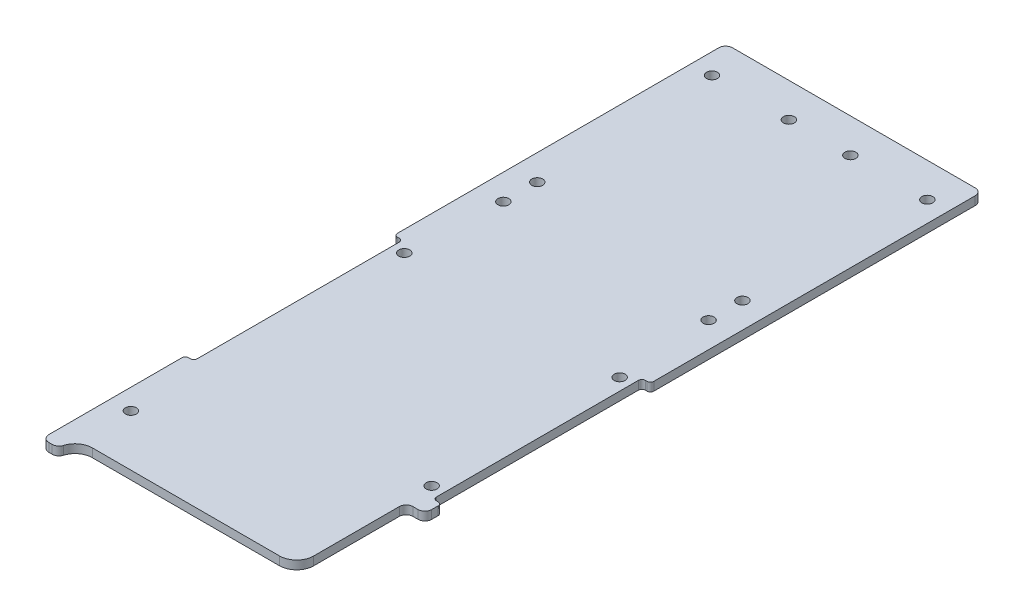
SolidWorks part; units mm, degrees
ref_plane "Front Plane" through (0, 0, 0) normal (0, 0, 1) x (1, 0, 0)
ref_plane "Top Plane" through (0, 0, 0) normal (0, 1, 0) x (1, 0, 0)
ref_plane "Right Plane" through (0, 0, 0) normal (1, 0, 0) x (0, 0, -1)
sketch "Sketch1" plane through (0, 0, 0) normal (0, 1, 0) x (1, 0, 0)
  line L0 (-39.9997, 0) -> (-39.9997, 114.3) construction
  line L1 (-47.625, 127) -> (47.625, 127)
  line L2 (-47.625, 127) -> (-47.625, -127)
  line L3 (-47.625, -127) -> (47.625, -127)
  line L4 (47.625, 127) -> (47.625, -127)
  line L5 (-47.625, 127) -> (47.625, -127) construction
  line L6 (-47.625, -127) -> (47.625, 127) construction
  line L7 (0, 0) -> (0, 127) construction
  line L8 (-39.9997, 0) -> (-39.9997, -101.6) construction
  line L9 (-39.9997, 0) -> (0, 0) construction
  line L10 (-41.275, -127) -> (-41.275, -120.65)
  line L11 (-41.275, -120.65) -> (41.275, -120.65)
  line L12 (41.275, -120.65) -> (41.275, -127)
  line L13 (-39.9997, 114.3) -> (-11.4247, 114.3) construction
  line L14 (39.9997, 114.3) -> (11.4247, 114.3) construction
  circle A0 centre (-39.9997, 114.3) radius 2.032
  circle A1 centre (-39.9997, 0) radius 2.032
  circle A2 centre (-39.9997, -101.6) radius 2.032
  circle A3 centre (39.9997, -101.6) radius 2.032
  circle A4 centre (39.9997, 0) radius 2.032
  circle A5 centre (39.9997, 114.3) radius 2.032
  circle A6 centre (-11.4247, 114.3) radius 2.032
  circle A7 centre (11.4247, 114.3) radius 2.032
  circle A8 centre (-39.9997, -69.85) radius 2.032
  circle A9 centre (39.9997, -69.85) radius 2.032
  point P0 (0, 0)
  dimension "D4" = 4.064
  dimension "D10" = 28.575
  dimension "D1" = 95.25
  dimension "D2" = 254
  dimension "D3" = 7.6253
  dimension "D5" = 12.7
  dimension "D6" = 25.4
  dimension "D7" = 6.35
  dimension "D8" = 6.35
  dimension "D9" = 6.35
  dimension "D11" = 69.85
extrude "Boss-Extrude1" add sketch "Sketch1" along normal blind 3.175 contours L4 L1 L2 L3 A4 A0 A1 A2 A3 A5 | A8 | A3 region at (0, 0, -2.6944) region at (39.9997, 0, 101.6) region at (-39.9997, 0, 69.85)
fillet "Fillet1" radius 2.54 4 edges at (-47.625, 1.5875, -127) (47.625, 1.5875, -127) (47.625, 1.5875, 127) (-47.625, 1.5875, 127)
fillet "Fillet2" radius 2.54 2 edges at (41.275, 1.5875, 127) (-41.275, 1.5875, 127)
fillet "Fillet3" radius 6.35 2 edges at (41.275, 1.5875, 120.65) (-41.275, 1.5875, 120.65)
sketch "Sketch2" plane through (0, 0, 0) normal (0, -1, 0) x (1, 0, 0)
  line L0 (41.9119, 131.8831) -> (41.9119, 109.8659) construction
  line L1 (41.9119, 109.8659) -> (41.9119, 106.3879) construction
  line L2 (41.9119, 83.271) -> (41.9119, 82.5325) construction
  line L3 (41.9119, 82.5325) -> (41.9119, 81.2514) construction
  line L4 (41.9119, 83.271) -> (41.9119, 106.3879) construction
  line L5 (41.9119, 131.8831) -> (41.9119, 109.8659)
  line L6 (41.9119, 109.8659) -> (41.9119, 106.3879)
  line L7 (41.9119, 83.271) -> (41.9119, 82.5325)
  line L8 (41.9119, 82.5325) -> (41.9119, 81.2514)
  line L9 (41.9119, 83.271) -> (41.9119, 106.3879)
  line L10 (41.9119, 81.2514) -> (47.625, 81.2514)
  line L11 (47.625, -124.46) -> (47.625, 124.46) construction
  line L12 (41.9119, 131.8831) -> (47.625, 131.8831)
  line L13 (47.625, 131.8831) -> (47.625, 81.2514)
  line L14 (40.6419, 79.9814) -> (48.895, 79.9814)
  line L15 (48.895, 133.1531) -> (48.895, 79.9814)
  line L16 (40.6419, 133.1531) -> (48.895, 133.1531)
  line L17 (40.6419, 133.1531) -> (40.6419, 109.8659)
  line L18 (40.6419, 109.8659) -> (40.6419, 106.3879)
  line L19 (40.6419, 83.271) -> (40.6419, 106.3879)
  line L20 (40.6419, 83.271) -> (40.6419, 82.5325)
  line L21 (40.6419, 82.5325) -> (40.6419, 79.9814)
  arc M7 (43.815, 127) -> (41.3809, 125.1857) centre (43.815, 124.46) ccw
  arc M8 (41.3809, 125.1857) -> (35.2956, 120.65) centre (35.2956, 127) cw
  line M18 (47.625, -124.46) -> (47.625, 124.46)
  dimension "D1" = 1.27
extrude "Cut-Extrude1" cut sketch "Sketch2" against normal through all contours L20 L21 L14 L10 L8 L7 L9 L19 M18 | L19 L9 L6 L5 L17 L18 M7 M8 | L13 L10 L8 L7 L9 L6 L5 L12 region at (41.6768, 0, 99.9813)
fillet "Fillet4" radius 6.35 1 edges at (40.6419, 1.5875, 123.5737)
fillet "Fillet5" radius 2.54 2 edges at (47.625, 1.5875, 79.9814) (40.6419, 1.5875, 79.9814)
sketch "Sketch3" plane through (0, 0, 0) normal (0, -1, 0) x (1, 0, 0)
  line L0 (-36.3087, -49.7791) -> (-39.9155, -49.7791) construction
  line L1 (-40.4235, -49.276) -> (-40.4235, -45.7043) construction
  line L2 (-35.8007, -45.7043) -> (-35.8007, -49.276) construction
  line L3 (-39.9155, -45.2013) -> (-36.3087, -45.2013) construction
  line L4 (-36.3087, -37.2027) -> (-39.9155, -37.2027) construction
  line L5 (-35.8007, -33.1279) -> (-35.8007, -36.6996) construction
  line L6 (-40.4235, -36.6996) -> (-40.4235, -33.1279) construction
  line L7 (-39.9155, -32.6249) -> (-36.3087, -32.6249) construction
  line L8 (36.2845, -32.6249) -> (39.8913, -32.6249) construction
  line L9 (40.3993, -33.1279) -> (40.3993, -36.6996) construction
  line L10 (39.8913, -37.2027) -> (36.2845, -37.2027) construction
  line L11 (35.7765, -36.6996) -> (35.7765, -33.1279) construction
  line L12 (36.2845, -45.2013) -> (39.8913, -45.2013) construction
  line L13 (35.7765, -49.276) -> (35.7765, -45.7043) construction
  line L14 (40.3993, -45.7043) -> (40.3993, -49.276) construction
  line L15 (39.8913, -49.7791) -> (36.2845, -49.7791) construction
  line L16 (-36.3087, -49.7791) -> (-39.9155, -49.7791)
  line L17 (-40.4235, -49.276) -> (-40.4235, -45.7043)
  line L18 (-35.8007, -45.7043) -> (-35.8007, -49.276)
  line L19 (-39.9155, -45.2013) -> (-36.3087, -45.2013)
  line L20 (-36.3087, -37.2027) -> (-39.9155, -37.2027)
  line L21 (-35.8007, -33.1279) -> (-35.8007, -36.6996)
  line L22 (-40.4235, -36.6996) -> (-40.4235, -33.1279)
  line L23 (-39.9155, -32.6249) -> (-36.3087, -32.6249)
  line L24 (36.2845, -32.6249) -> (39.8913, -32.6249)
  line L25 (40.3993, -33.1279) -> (40.3993, -36.6996)
  line L26 (39.8913, -37.2027) -> (36.2845, -37.2027)
  line L27 (35.7765, -36.6996) -> (35.7765, -33.1279)
  line L28 (36.2845, -45.2013) -> (39.8913, -45.2013)
  line L29 (35.7765, -49.276) -> (35.7765, -45.7043)
  line L30 (40.3993, -45.7043) -> (40.3993, -49.276)
  line L31 (39.8913, -49.7791) -> (36.2845, -49.7791)
  line L32 (-47.625, -25.836) -> (47.625, -25.836)
  line L33 (-47.625, -124.46) -> (-47.625, 124.46) construction
  line L34 (47.625, -124.46) -> (47.625, 77.4414) construction
  line L35 (0, -25.836) -> (0, -56.0686) construction
  line L38 (134.3621, -51.414) -> (184.1379, -51.414)
  line L39 (184.1379, -51.414) -> (184.1379, -43.4909)
  line L40 (184.1379, -43.4909) -> (182.3345, -43.4909)
  line L41 (181.8265, -42.9878) -> (181.8265, -39.4161)
  line L42 (182.3345, -38.9131) -> (184.1379, -38.9131)
  line L43 (184.1379, -38.9131) -> (184.1379, -30.9899)
  line L44 (184.1379, -30.9899) -> (134.3621, -30.9899)
  line L45 (134.3621, -30.9899) -> (133.3379, -32.0042)
  line L46 (133.3379, -32.0042) -> (132.3138, -30.9899)
  line L47 (132.3138, -30.9899) -> (70.8621, -30.9899)
  line L48 (70.8621, -30.9899) -> (69.8379, -32.0042)
  line L49 (69.8379, -32.0042) -> (68.8138, -30.9899)
  line L50 (68.8138, -30.9899) -> (7.3621, -30.9899)
  line L51 (7.3621, -30.9899) -> (6.3379, -32.0042)
  line L52 (6.3379, -32.0042) -> (5.3138, -30.9899)
  line L53 (5.3138, -30.9899) -> (-56.1379, -30.9899)
  line L54 (-56.1379, -30.9899) -> (-57.1621, -32.0042)
  line L55 (-57.1621, -32.0042) -> (-58.1862, -30.9899)
  line L56 (-58.1862, -30.9899) -> (-119.6379, -30.9899)
  line L57 (-119.6379, -30.9899) -> (-120.6621, -32.0042)
  line L58 (-120.6621, -32.0042) -> (-121.6862, -30.9899)
  line L59 (-121.6862, -30.9899) -> (-184.1621, -30.9899)
  line L60 (-184.1621, -30.9899) -> (-184.1621, -51.414)
  line L61 (-184.1621, -51.414) -> (-121.6862, -51.414)
  line L62 (-121.6862, -51.414) -> (-120.6621, -50.3998)
  line L63 (-120.6621, -50.3998) -> (-119.6379, -51.414)
  line L64 (-119.6379, -51.414) -> (-58.1862, -51.414)
  line L65 (-58.1862, -51.414) -> (-57.1621, -50.3998)
  line L66 (-57.1621, -50.3998) -> (-56.1379, -51.414)
  line L67 (-56.1379, -51.414) -> (5.3138, -51.414)
  line L68 (5.3138, -51.414) -> (6.3379, -50.3998)
  line L69 (6.3379, -50.3998) -> (7.3621, -51.414)
  line L70 (7.3621, -51.414) -> (68.8138, -51.414)
  line L71 (68.8138, -51.414) -> (69.8379, -50.3998)
  line L72 (69.8379, -50.3998) -> (70.8621, -51.414)
  line L73 (70.8621, -51.414) -> (132.3138, -51.414)
  line L74 (132.3138, -51.414) -> (133.3379, -50.3998)
  line L75 (133.3379, -50.3998) -> (134.3621, -51.414)
  line L76 (134.3621, -51.414) -> (184.1379, -51.414)
  line L77 (184.1379, -51.414) -> (184.1379, -43.4909)
  line L78 (184.1379, -43.4909) -> (182.3345, -43.4909)
  line L79 (181.8265, -42.9878) -> (181.8265, -39.4161)
  line L80 (182.3345, -38.9131) -> (184.1379, -38.9131)
  line L81 (184.1379, -38.9131) -> (184.1379, -30.9899)
  line L82 (184.1379, -30.9899) -> (134.3621, -30.9899)
  line L83 (134.3621, -30.9899) -> (133.3379, -32.0042)
  line L84 (133.3379, -32.0042) -> (132.3138, -30.9899)
  line L85 (132.3138, -30.9899) -> (70.8621, -30.9899)
  line L86 (70.8621, -30.9899) -> (69.8379, -32.0042)
  line L87 (69.8379, -32.0042) -> (68.8138, -30.9899)
  line L88 (68.8138, -30.9899) -> (7.3621, -30.9899)
  line L89 (7.3621, -30.9899) -> (6.3379, -32.0042)
  line L90 (6.3379, -32.0042) -> (5.3138, -30.9899)
  line L91 (5.3138, -30.9899) -> (-56.1379, -30.9899)
  line L92 (-56.1379, -30.9899) -> (-57.1621, -32.0042)
  line L93 (-57.1621, -32.0042) -> (-58.1862, -30.9899)
  line L94 (-58.1862, -30.9899) -> (-119.6379, -30.9899)
  line L95 (-119.6379, -30.9899) -> (-120.6621, -32.0042)
  line L96 (-120.6621, -32.0042) -> (-121.6862, -30.9899)
  line L97 (-121.6862, -30.9899) -> (-184.1621, -30.9899)
  line L98 (-184.1621, -30.9899) -> (-184.1621, -51.414)
  line L99 (-184.1621, -51.414) -> (-121.6862, -51.414)
  line L100 (-121.6862, -51.414) -> (-120.6621, -50.3998)
  line L101 (-120.6621, -50.3998) -> (-119.6379, -51.414)
  line L102 (-119.6379, -51.414) -> (-58.1862, -51.414)
  line L103 (-58.1862, -51.414) -> (-57.1621, -50.3998)
  line L104 (-57.1621, -50.3998) -> (-56.1379, -51.414)
  line L105 (-56.1379, -51.414) -> (5.3138, -51.414)
  line L106 (5.3138, -51.414) -> (6.3379, -50.3998)
  line L107 (6.3379, -50.3998) -> (7.3621, -51.414)
  line L108 (7.3621, -51.414) -> (68.8138, -51.414)
  line L109 (68.8138, -51.414) -> (69.8379, -50.3998)
  line L110 (69.8379, -50.3998) -> (70.8621, -51.414)
  line L111 (70.8621, -51.414) -> (132.3138, -51.414)
  line L112 (132.3138, -51.414) -> (133.3379, -50.3998)
  line L113 (133.3379, -50.3998) -> (134.3621, -51.414)
  line L1362 (-40.4235, -34.9138) -> (-35.8007, -34.9138)
  line L1857 (-38.1121, -32.6249) -> (-38.1121, -37.2027)
  line L1858 (-38.1121, -45.2013) -> (-38.1121, -49.7791)
  line L1859 (-40.4235, -47.4902) -> (-35.8007, -47.4902)
  circle A0 centre (-38.1121, -34.9138) radius 2.032
  circle A1 centre (-38.1121, -47.4902) radius 2.032
  circle A2 centre (38.1121, -47.4902) radius 2.032
  circle A3 centre (38.1121, -34.9138) radius 2.032
  ellipse E0 centre (-39.9155, -45.7043) end of major axis (-39.4075, -45.7043) minor radius 0.5031 (-39.9155, -45.2013) -> (-40.4235, -45.7043) ccw construction
  ellipse E1 centre (-39.9155, -49.276) end of major axis (-39.4075, -49.276) minor radius 0.5031 (-40.4235, -49.276) -> (-39.9155, -49.7791) ccw construction
  ellipse E2 centre (182.3345, -42.9878) end of major axis (182.8425, -42.9878) minor radius 0.5031 (181.8265, -42.9878) -> (182.3345, -43.4909) ccw
  ellipse E3 centre (182.3345, -39.4161) end of major axis (182.8425, -39.4161) minor radius 0.5031 (182.3345, -38.9131) -> (181.8265, -39.4161) ccw
  ellipse E4 centre (182.3345, -42.9878) end of major axis (182.8425, -42.9878) minor radius 0.5031 (181.8265, -42.9878) -> (182.3345, -43.4909) ccw
  ellipse E5 centre (182.3345, -39.4161) end of major axis (182.8425, -39.4161) minor radius 0.5031 (182.3345, -38.9131) -> (181.8265, -39.4161) ccw
  ellipse E6 centre (-36.3087, -49.276) end of major axis (-35.8007, -49.276) minor radius 0.5031 (-36.3087, -49.7791) -> (-35.8007, -49.276) ccw construction
  ellipse E7 centre (-36.3087, -45.7043) end of major axis (-35.8007, -45.7043) minor radius 0.5031 (-35.8007, -45.7043) -> (-36.3087, -45.2013) ccw construction
  ellipse E8 centre (-39.9155, -36.6996) end of major axis (-39.4075, -36.6996) minor radius 0.5031 (-40.4235, -36.6996) -> (-39.9155, -37.2027) ccw construction
  ellipse E9 centre (-36.3087, -36.6996) end of major axis (-35.8007, -36.6996) minor radius 0.5031 (-36.3087, -37.2027) -> (-35.8007, -36.6996) ccw construction
  ellipse E10 centre (-36.3087, -33.1279) end of major axis (-35.8007, -33.1279) minor radius 0.5031 (-35.8007, -33.1279) -> (-36.3087, -32.6249) ccw construction
  ellipse E11 centre (-39.9155, -33.1279) end of major axis (-39.4075, -33.1279) minor radius 0.5031 (-39.9155, -32.6249) -> (-40.4235, -33.1279) ccw construction
  ellipse E12 centre (39.8913, -33.1279) end of major axis (40.3993, -33.1279) minor radius 0.5031 (40.3993, -33.1279) -> (39.8913, -32.6249) ccw construction
  ellipse E13 centre (36.2845, -33.1279) end of major axis (36.7925, -33.1279) minor radius 0.5031 (36.2845, -32.6249) -> (35.7765, -33.1279) ccw construction
  ellipse E14 centre (39.8913, -36.6996) end of major axis (40.3993, -36.6996) minor radius 0.5031 (39.8913, -37.2027) -> (40.3993, -36.6996) ccw construction
  ellipse E15 centre (36.2845, -36.6996) end of major axis (36.7925, -36.6996) minor radius 0.5031 (35.7765, -36.6996) -> (36.2845, -37.2027) ccw construction
  ellipse E16 centre (36.2845, -45.7043) end of major axis (36.7925, -45.7043) minor radius 0.5031 (36.2845, -45.2013) -> (35.7765, -45.7043) ccw construction
  ellipse E17 centre (36.2845, -49.276) end of major axis (36.7925, -49.276) minor radius 0.5031 (35.7765, -49.276) -> (36.2845, -49.7791) ccw construction
  ellipse E18 centre (39.8913, -45.7043) end of major axis (40.3993, -45.7043) minor radius 0.5031 (40.3993, -45.7043) -> (39.8913, -45.2013) ccw construction
  ellipse E19 centre (39.8913, -49.276) end of major axis (40.3993, -49.276) minor radius 0.5031 (39.8913, -49.7791) -> (40.3993, -49.276) ccw construction
  ellipse E20 centre (-39.9155, -45.7043) end of major axis (-39.4075, -45.7043) minor radius 0.5031 (-39.9155, -45.2013) -> (-40.4235, -45.7043) ccw
  ellipse E21 centre (-39.9155, -49.276) end of major axis (-39.4075, -49.276) minor radius 0.5031 (-40.4235, -49.276) -> (-39.9155, -49.7791) ccw
  ellipse E22 centre (-36.3087, -49.276) end of major axis (-35.8007, -49.276) minor radius 0.5031 (-36.3087, -49.7791) -> (-35.8007, -49.276) ccw
  ellipse E23 centre (-36.3087, -45.7043) end of major axis (-35.8007, -45.7043) minor radius 0.5031 (-35.8007, -45.7043) -> (-36.3087, -45.2013) ccw
  ellipse E24 centre (-39.9155, -36.6996) end of major axis (-39.4075, -36.6996) minor radius 0.5031 (-40.4235, -36.6996) -> (-39.9155, -37.2027) ccw
  ellipse E25 centre (-36.3087, -36.6996) end of major axis (-35.8007, -36.6996) minor radius 0.5031 (-36.3087, -37.2027) -> (-35.8007, -36.6996) ccw
  ellipse E26 centre (-36.3087, -33.1279) end of major axis (-35.8007, -33.1279) minor radius 0.5031 (-35.8007, -33.1279) -> (-36.3087, -32.6249) ccw
  ellipse E27 centre (-39.9155, -33.1279) end of major axis (-39.4075, -33.1279) minor radius 0.5031 (-39.9155, -32.6249) -> (-40.4235, -33.1279) ccw
  ellipse E28 centre (39.8913, -33.1279) end of major axis (40.3993, -33.1279) minor radius 0.5031 (40.3993, -33.1279) -> (39.8913, -32.6249) ccw
  ellipse E29 centre (36.2845, -33.1279) end of major axis (36.7925, -33.1279) minor radius 0.5031 (36.2845, -32.6249) -> (35.7765, -33.1279) ccw
  ellipse E30 centre (39.8913, -36.6996) end of major axis (40.3993, -36.6996) minor radius 0.5031 (39.8913, -37.2027) -> (40.3993, -36.6996) ccw
  ellipse E31 centre (36.2845, -36.6996) end of major axis (36.7925, -36.6996) minor radius 0.5031 (35.7765, -36.6996) -> (36.2845, -37.2027) ccw
  ellipse E32 centre (36.2845, -45.7043) end of major axis (36.7925, -45.7043) minor radius 0.5031 (36.2845, -45.2013) -> (35.7765, -45.7043) ccw
  ellipse E33 centre (36.2845, -49.276) end of major axis (36.7925, -49.276) minor radius 0.5031 (35.7765, -49.276) -> (36.2845, -49.7791) ccw
  ellipse E34 centre (39.8913, -45.7043) end of major axis (40.3993, -45.7043) minor radius 0.5031 (40.3993, -45.7043) -> (39.8913, -45.2013) ccw
  ellipse E35 centre (39.8913, -49.276) end of major axis (40.3993, -49.276) minor radius 0.5031 (39.8913, -49.7791) -> (40.3993, -49.276) ccw
  dimension "D2" = 4.064
  dimension "D1" = 0
extrude "Cut-Extrude2" cut sketch "Sketch3" against normal through all contours A0 | A1 | A2 | A3
sketch "Sketch4" plane through (0, 3.175, 0) normal (0, 1, 0) x (1, 0, 0)
  line L0 (-44.45, 3.81) -> (-46.99, 3.81) construction
  line L1 (-46.99, 3.81) -> (-46.99, 121.92) construction
  line L2 (-42.545, 126.365) -> (-0.635, 126.365) construction
  line L3 (-0.635, 126.365) -> (-0.635, 107.95) construction
  line L4 (-6.35, 102.235) -> (-15.875, 102.235) construction
  line L5 (-22.86, 95.25) -> (-22.86, -115.57) construction
  line L6 (-27.305, -120.015) -> (-35.4551, -120.015) construction
  line L7 (-43.815, -126.365) -> (-45.085, -126.365) construction
  line L8 (-46.99, -124.46) -> (-46.99, -73.7819) construction
  line L9 (-46.99, -73.7819) -> (-44.45, -73.7819) construction
  line L10 (-44.45, -73.7819) -> (-44.45, 3.81) construction
  line L11 (-46.99, 3.81) -> (-44.45, 3.81)
  line L12 (-46.99, 121.92) -> (-46.99, 3.81)
  line L13 (-0.635, 126.365) -> (-42.545, 126.365)
  line L14 (-0.635, 107.95) -> (-0.635, 126.365)
  line L15 (-15.875, 102.235) -> (-6.35, 102.235)
  line L16 (-22.86, -115.57) -> (-22.86, 95.25)
  line L17 (-35.4551, -120.015) -> (-27.305, -120.015)
  line L18 (-45.085, -126.365) -> (-43.815, -126.365)
  line L19 (-46.99, -73.7819) -> (-46.99, -124.46)
  line L20 (-44.45, -73.7819) -> (-46.99, -73.7819)
  line L21 (-44.45, 3.81) -> (-44.45, -73.7819)
  line L22 (-46.99, 3.81) -> (-44.45, 3.81)
  line L23 (-46.99, 121.92) -> (-46.99, 3.81)
  line L24 (-0.635, 126.365) -> (-42.545, 126.365)
  line L25 (-0.635, 107.95) -> (-0.635, 126.365)
  line L26 (-15.875, 102.235) -> (-6.35, 102.235)
  line L27 (-22.86, -115.57) -> (-22.86, 95.25)
  line L28 (-35.4551, -120.015) -> (-27.305, -120.015)
  line L29 (-45.085, -126.365) -> (-43.815, -126.365)
  line L30 (-46.99, -73.7819) -> (-46.99, -124.46)
  line L31 (-44.45, -73.7819) -> (-46.99, -73.7819)
  line L32 (-44.45, 3.81) -> (-44.45, -73.7819)
  line L33 (40.64, -77.5286) -> (40.64, -117.0408) construction
  line L34 (35.4551, -120.015) -> (27.305, -120.015) construction
  line L35 (22.86, -115.57) -> (22.86, 95.25) construction
  line L36 (15.875, 102.235) -> (6.35, 102.235) construction
  line L37 (0.635, 107.95) -> (0.635, 126.365) construction
  line L38 (0.635, 126.365) -> (42.545, 126.365) construction
  line L39 (46.99, 121.92) -> (46.99, 3.81) construction
  line L40 (46.99, 3.81) -> (44.45, 3.81) construction
  line L41 (44.45, 3.81) -> (44.45, -73.7819) construction
  line L42 (44.45, -73.7819) -> (46.99, -73.7819) construction
  line L43 (46.99, -73.7819) -> (46.99, -77.5286) construction
  line L44 (46.99, -77.5286) -> (40.64, -77.5286) construction
  line L45 (-44.45, 3.81) -> (-46.99, 3.81)
  line L46 (-46.99, 3.81) -> (-46.99, 121.92)
  line L47 (-42.545, 126.365) -> (-0.635, 126.365)
  line L48 (-0.635, 126.365) -> (-0.635, 107.95)
  line L49 (-6.35, 102.235) -> (-15.875, 102.235)
  line L50 (-22.86, 95.25) -> (-22.86, -115.57)
  line L51 (-27.305, -120.015) -> (-35.4551, -120.015)
  line L52 (-43.815, -126.365) -> (-45.085, -126.365)
  line L53 (-46.99, -124.46) -> (-46.99, -73.7819)
  line L54 (-46.99, -73.7819) -> (-44.45, -73.7819)
  line L55 (-44.45, -73.7819) -> (-44.45, 3.81)
  line L56 (40.64, -77.5286) -> (40.64, -117.0408)
  line L57 (35.4551, -120.015) -> (27.305, -120.015)
  line L58 (22.86, -115.57) -> (22.86, 95.25)
  line L59 (15.875, 102.235) -> (6.35, 102.235)
  line L60 (0.635, 107.95) -> (0.635, 126.365)
  line L61 (0.635, 126.365) -> (42.545, 126.365)
  line L62 (46.99, 121.92) -> (46.99, 3.81)
  line L63 (46.99, 3.81) -> (44.45, 3.81)
  line L64 (44.45, 3.81) -> (44.45, -73.7819)
  line L65 (44.45, -73.7819) -> (46.99, -73.7819)
  line L66 (46.99, -73.7819) -> (46.99, -77.5286)
  line L67 (46.99, -77.5286) -> (40.64, -77.5286)
  line L178 (-46.99, 3.81) -> (-47.625, 3.81)
  line L179 (-47.625, 124.46) -> (-47.625, -124.46) construction
  line L180 (-46.99, -73.7819) -> (-47.625, -73.7819)
  line L181 (46.99, -73.7819) -> (47.625, -73.7819)
  line L182 (47.625, 124.46) -> (47.625, -77.4414) construction
  line L183 (46.99, 3.81) -> (47.625, 3.81)
  arc A0 (-42.545, 126.365) -> (-46.99, 121.92) centre (-42.545, 121.92) ccw construction
  arc A1 (-6.35, 102.235) -> (-0.635, 107.95) centre (-6.35, 107.95) ccw construction
  arc A2 (-15.875, 102.235) -> (-22.86, 95.25) centre (-15.875, 95.25) ccw construction
  arc A3 (-27.305, -120.015) -> (-22.86, -115.57) centre (-27.305, -115.57) ccw construction
  arc A4 (-35.4551, -120.015) -> (-41.9138, -124.3399) centre (-35.4551, -127) ccw construction
  arc A5 (-43.815, -126.365) -> (-41.9138, -124.3399) centre (-43.815, -124.46) ccw construction
  arc A6 (-46.99, -124.46) -> (-45.085, -126.365) centre (-45.085, -124.46) ccw construction
  arc A7 (-42.545, 126.365) -> (-46.99, 121.92) centre (-42.545, 121.92) ccw
  arc A8 (-6.35, 102.235) -> (-0.635, 107.95) centre (-6.35, 107.95) ccw
  arc A9 (-15.875, 102.235) -> (-22.86, 95.25) centre (-15.875, 95.25) ccw
  arc A10 (-27.305, -120.015) -> (-22.86, -115.57) centre (-27.305, -115.57) ccw
  arc A11 (-35.4551, -120.015) -> (-41.9138, -124.3399) centre (-35.4551, -127) ccw
  arc A12 (-43.815, -126.365) -> (-41.9138, -124.3399) centre (-43.815, -124.46) ccw
  arc A13 (-46.99, -124.46) -> (-45.085, -126.365) centre (-45.085, -124.46) ccw
  arc A14 (-42.545, 126.365) -> (-46.99, 121.92) centre (-42.545, 121.92) ccw
  arc A15 (-6.35, 102.235) -> (-0.635, 107.95) centre (-6.35, 107.95) ccw
  arc A16 (-15.875, 102.235) -> (-22.86, 95.25) centre (-15.875, 95.25) ccw
  arc A17 (-27.305, -120.015) -> (-22.86, -115.57) centre (-27.305, -115.57) ccw
  arc A18 (-35.4551, -120.015) -> (-41.9138, -124.3399) centre (-35.4551, -127) ccw
  arc A19 (-43.815, -126.365) -> (-41.9138, -124.3399) centre (-43.815, -124.46) ccw
  arc A20 (-46.99, -124.46) -> (-45.085, -126.365) centre (-45.085, -124.46) ccw
  arc A21 (36.8369, -120.153) -> (40.64, -117.0408) centre (37.465, -117.0408) ccw construction
  arc A22 (36.8369, -120.153) -> (35.4551, -120.015) centre (35.4551, -127) ccw construction
  arc A23 (22.86, -115.57) -> (27.305, -120.015) centre (27.305, -115.57) ccw construction
  arc A24 (22.86, 95.25) -> (15.875, 102.235) centre (15.875, 95.25) ccw construction
  arc A25 (0.635, 107.95) -> (6.35, 102.235) centre (6.35, 107.95) ccw construction
  arc A26 (46.99, 121.92) -> (42.545, 126.365) centre (42.545, 121.92) ccw construction
  arc A27 (-42.545, 126.365) -> (-46.99, 121.92) centre (-42.545, 121.92) ccw
  arc A28 (-6.35, 102.235) -> (-0.635, 107.95) centre (-6.35, 107.95) ccw
  arc A29 (-15.875, 102.235) -> (-22.86, 95.25) centre (-15.875, 95.25) ccw
  arc A30 (-27.305, -120.015) -> (-22.86, -115.57) centre (-27.305, -115.57) ccw
  arc A31 (-35.4551, -120.015) -> (-41.9138, -124.3399) centre (-35.4551, -127) ccw
  arc A32 (-43.815, -126.365) -> (-41.9138, -124.3399) centre (-43.815, -124.46) ccw
  arc A33 (-46.99, -124.46) -> (-45.085, -126.365) centre (-45.085, -124.46) ccw
  arc A34 (36.8369, -120.153) -> (40.64, -117.0408) centre (37.465, -117.0408) ccw
  arc A35 (36.8369, -120.153) -> (35.4551, -120.015) centre (35.4551, -127) ccw
  arc A36 (22.86, -115.57) -> (27.305, -120.015) centre (27.305, -115.57) ccw
  arc A37 (22.86, 95.25) -> (15.875, 102.235) centre (15.875, 95.25) ccw
  arc A38 (0.635, 107.95) -> (6.35, 102.235) centre (6.35, 107.95) ccw
  arc A39 (46.99, 121.92) -> (42.545, 126.365) centre (42.545, 121.92) ccw
  line M32 (47.625, -77.4414) -> (47.625, 124.46)
  line M36 (-47.625, 124.46) -> (-47.625, -124.46)
  dimension "D1" = 0
extrude "Cut-Extrude3" cut sketch "Sketch4" against normal through all and the other way through all contours L180 L31 L32 L22 L178 M36 | L183 L63 L64 L65 L181 M32 region at (-46.0375, 3.175, 34.9859) region at (46.0375, 3.175, 34.9859)
fillet "Fillet6" radius 1.27 8 edges at (-44.45, 1.5875, -3.81) (-44.45, 1.5875, 73.7819) (44.45, 1.5875, -3.81) (44.45, 1.5875, 73.7819) (47.625, 1.5875, 73.7819) (47.625, 1.5875, -3.81) (-47.625, 1.5875, 73.7819) (-47.625, 1.5875, -3.81)
